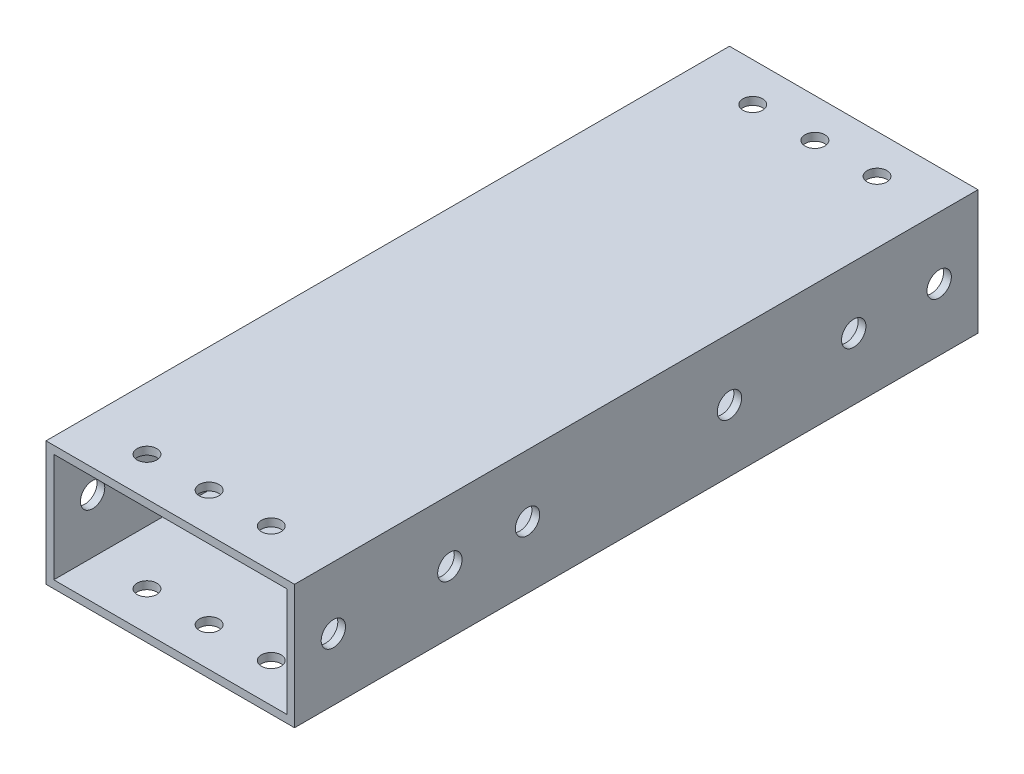
SolidWorks part; units mm, degrees
material "6061-T6 (SS)"
ref_plane "Front Plane" through (0, 0, 0) normal (0, 0, 1) x (1, 0, 0)
ref_plane "Top Plane" through (0, 0, 0) normal (0, 1, 0) x (1, 0, 0)
ref_plane "Right Plane" through (0, 0, 0) normal (1, 0, 0) x (0, 0, -1)
sketch "Sketch1" plane through (0, 0, 0) normal (0, 0, 1) x (1, 0, 0)
  line L0 (-23.8125, 11.1125) -> (23.8125, 11.1125)
  line L1 (-25.4, -12.7) -> (25.4, -12.7)
  line L2 (-25.4, -12.7) -> (-25.4, 12.7)
  line L3 (-25.4, 12.7) -> (25.4, 12.7)
  line L4 (25.4, -12.7) -> (25.4, 12.7)
  line L5 (-25.4, -12.7) -> (25.4, 12.7) construction
  line L6 (-25.4, 12.7) -> (25.4, -12.7) construction
  line L7 (23.8125, -11.1125) -> (23.8125, 11.1125)
  line L8 (-23.8125, -11.1125) -> (23.8125, -11.1125)
  line L9 (-23.8125, -11.1125) -> (-23.8125, 11.1125)
  point P0 (0, 0)
  dimension "D1" = 50.8
  dimension "D2" = 25.4
  dimension "D3" = 1.5875
extrude "Boss-Extrude1" add sketch "Sketch1" along normal mid plane 139.7
sketch "Sketch2" plane through (0, 12.7, 0) normal (0, 1, 0) x (1, 0, 0)
  line L0 (25.4, 69.85) -> (-25.4, 69.85) construction
  line L1 (25.4, 0) -> (-25.4, 0) construction
  line L2 (25.4, -69.85) -> (25.4, 69.85) construction
  line L3 (-25.4, -69.85) -> (-25.4, 69.85) construction
  circle A0 centre (-12.7, 61.9125) radius 2.0193
  circle A1 centre (0, 61.9125) radius 2.0193
  circle A2 centre (12.7, 61.9125) radius 2.0193
  circle A3 centre (12.7, -61.9125) radius 2.0193
  circle A4 centre (0, -61.9125) radius 2.0193
  circle A5 centre (-12.7, -61.9125) radius 2.0193
  dimension "D1" = 4.0386
  dimension "D2" = 12.7
  dimension "D3" = 12.7
  dimension "D4" = 7.9375
extrude "Cut-Extrude1" cut sketch "Sketch2" against normal through all
sketch "Sketch3" plane through (25.4, 0, 0) normal (1, 0, 0) x (0, 0, -1)
  line L0 (0, 12.7) -> (0, -12.7) construction
  line L1 (-69.85, 12.7) -> (69.85, 12.7) construction
  line L2 (-69.85, -12.7) -> (69.85, -12.7) construction
  line L3 (-69.85, -12.7) -> (-69.85, 12.7) construction
  line L5 (69.85, -12.7) -> (69.85, 12.7) construction
  circle A8 centre (61.9125, 0) radius 2.4892
  circle A9 centre (44.45, 0) radius 2.4892
  circle A10 centre (19.05, 0) radius 2.4892
  circle A11 centre (-61.9125, 0) radius 2.4892
  circle A14 centre (-38.1, 0) radius 2.4892
  circle A15 centre (-22.225, 0) radius 2.4892
  dimension "D1" = 7.9375
  dimension "D3" = 15.875
  dimension "D8" = 4.9784
  dimension "D2" = 31.75
  dimension "D4" = 25.4
  dimension "D7" = 25.4
extrude "Cut-Extrude2" cut sketch "Sketch3" against normal through all
